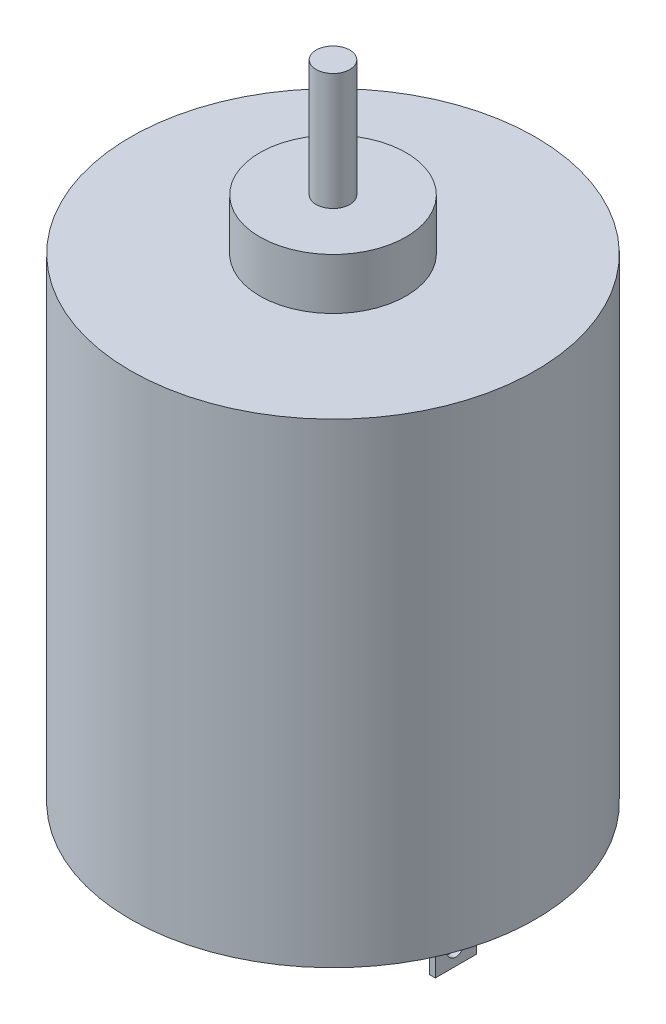
SolidWorks part; units mm, degrees
ref_plane "Plan de face" through (0, 0, 0) normal (0, 0, 1) x (1, 0, 0)
ref_plane "Plan de dessus" through (0, 0, 0) normal (0, 1, 0) x (1, 0, 0)
ref_plane "Plan de droite" through (0, 0, 0) normal (1, 0, 0) x (0, 0, -1)
sketch "Esquisse1" plane through (0, 0, 0) normal (0, 1, 0) x (1, 0, 0)
  line L0 (0, 0) -> (-13.85, 0) construction
  line L1 (-8.4, 1.4) -> (-8, 1.4)
  line L2 (-8.4, 1.4) -> (-8.4, -1.4)
  line L3 (-8.4, -1.4) -> (-8, -1.4)
  line L4 (-8, 1.4) -> (-8, -1.4)
  line L5 (0, 0) -> (13.85, 0) construction
  line L7 (8, 1.4) -> (8.4, 1.4)
  line L8 (8, 1.4) -> (8, -1.4)
  line L9 (8, -1.4) -> (8.4, -1.4)
  line L10 (8.4, 1.4) -> (8.4, -1.4)
  circle A0 centre (0, 0) radius 13.85
  circle A1 centre (0, 0) radius 1.1525
  circle A2 centre (0, 0) radius 5
  dimension "D1" = 27.7
  dimension "D2" = 2.305
  dimension "D3" = 10
  dimension "D4" = 0.4
  dimension "D5" = 1.4
  dimension "D6" = 1.4
  dimension "D7" = 8
  dimension "D8" = 0.4
  dimension "D9" = 8
  dimension "D10" = 1.4
  dimension "D11" = 1.4
extrude "Boss.-Extru.1" add sketch "Esquisse1" along normal blind 32.5 contours A0
extrude "Boss.-Extru.2" add sketch "Esquisse1<3>" along normal blind 36 and the other way blind 2.2 contours A2
sketch "Esquisse1<3>" plane through (0, 0, 0) normal (0, 1, 0) x (1, 0, 0) same geometry as "Esquisse1"
extrude "Boss.-Extru.3" add sketch "Esquisse1<4>" along normal blind 44 and the other way blind 3 contours A1
sketch "Esquisse1<4>" plane through (0, 0, 0) normal (0, 1, 0) x (1, 0, 0) same geometry as "Esquisse1"
extrude "Boss.-Extru.4" add sketch "Esquisse1<5>" against normal blind 5.5 contours L8 L9 L10 L7 | L2 L3 L4 L1
sketch "Esquisse1<5>" plane through (0, 0, 0) normal (0, 1, 0) x (1, 0, 0) same geometry as "Esquisse1"
sketch "Esquisse2" plane through (-8.4, 0, 0) normal (-1, 0, 0) x (0, 0, 1)
  ellipse E0 centre (0, -3.6976) end of major axis (0, -2.4338) minor radius 0.8054
extrude "Enlèv. mat.-Extru.2" cut sketch "Esquisse2" against normal up to next contours E0
sketch "Esquisse3" plane through (8.4, 0, 0) normal (1, 0, 0) x (0, 0, -1)
  ellipse E0 centre (0, -3.6976) end of major axis (0, -4.9613) minor radius 0.8054
  ellipse E1 centre (0, -3.6976) end of major axis (0, -2.4338) minor radius 0.8054 construction
extrude "Enlèv. mat.-Extru.3" cut sketch "Esquisse3" against normal up to next contours E0
